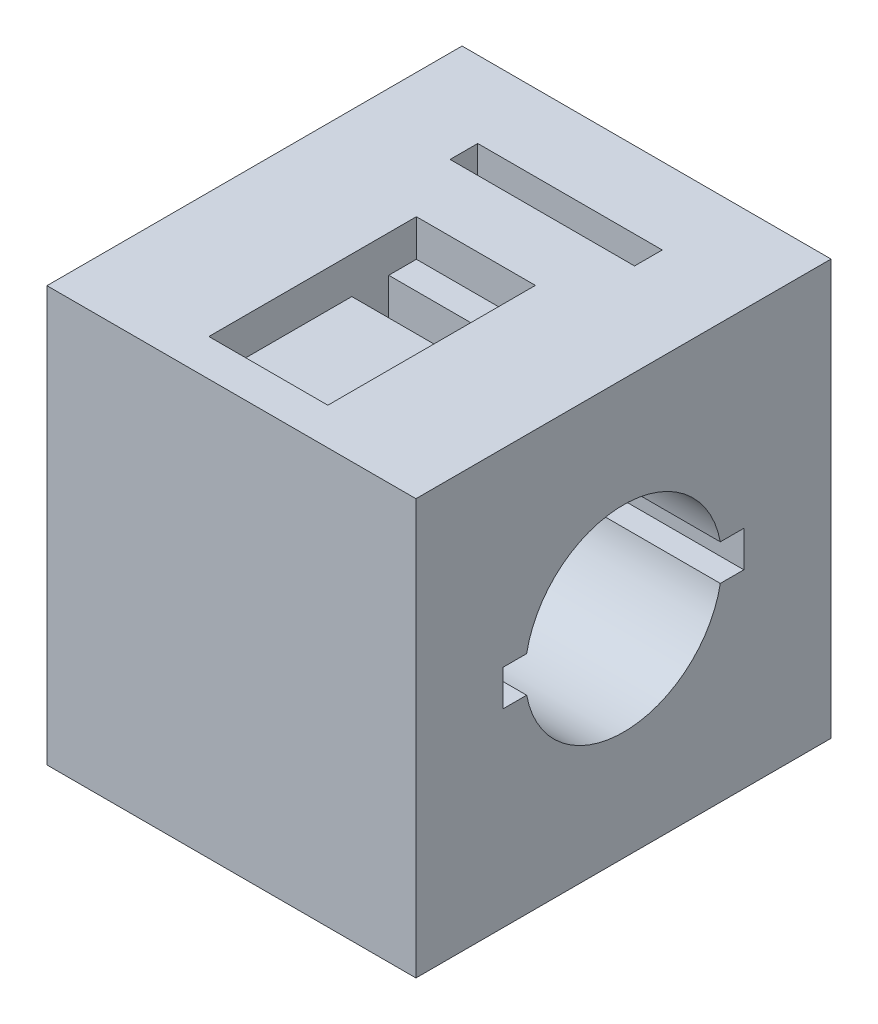
SolidWorks part; units mm, degrees
ref_plane "Front Plane" through (0, 0, 0) normal (0, 0, 1) x (1, 0, 0)
ref_plane "Top Plane" through (0, 0, 0) normal (0, 1, 0) x (1, 0, 0)
ref_plane "Right Plane" through (0, 0, 0) normal (1, 0, 0) x (0, 0, -1)
sketch "Sketch1" plane through (0, 0, 0) normal (1, 0, 0) x (0, 0, -1)
  line L1 (-22.5, 22.5) -> (22.5, 22.5)
  line L2 (-22.5, 22.5) -> (-22.5, -22.5)
  line L3 (-22.5, -22.5) -> (22.5, -22.5)
  line L4 (22.5, 22.5) -> (22.5, -22.5)
  line L5 (-22.5, 22.5) -> (22.5, -22.5) construction
  line L6 (-22.5, -22.5) -> (22.5, 22.5) construction
  point P0 (0, 0)
  dimension "D1" = 45
  dimension "D2" = 45
extrude "Boss-Extrude1" add sketch "Sketch1" along normal blind 40
sketch "Sketch2" plane through (40, 0, 0) normal (1, 0, 0) x (0, 0, -1)
  circle A0 centre (0, 0) radius 10.675
  dimension "D1" = 21.35
extrude "Cut-Extrude1" cut sketch "Sketch2" against normal through all
sketch "Sketch3" plane through (40, 0, 0) normal (1, 0, 0) x (0, 0, -1)
  line L0 (10.4954, 1.95) -> (13.0454, 1.95)
  line L1 (13.0454, 1.95) -> (13.0454, -1.95)
  line L2 (13.0454, -1.95) -> (10.4954, -1.95)
  circle A0 centre (0, 0) radius 10.675 construction
  arc A1 (10.4954, 1.95) -> (10.4954, -1.95) centre (10.4954, 0) ccw
  point P6 (13.0454, 0)
  dimension "D1" = 2.55
  dimension "D2" = 3.9
extrude "Cut-Extrude2" cut sketch "Sketch3" against normal through all
mirror "Mirror1" about plane through (0, 0, 0) normal (0, 0, 1) of "Cut-Extrude2"
sketch "Sketch4" plane through (0, 22.5, 0) normal (0, 1, 0) x (1, 0, 0)
  line L0 (20, 22.5) -> (20, -22.5) construction
  line L1 (40, 22.5) -> (0, 22.5) construction
  line L2 (40, -22.5) -> (0, -22.5) construction
  line L4 (13.55, 4) -> (26.45, 4)
  line L5 (13.55, 4) -> (13.55, -18.5)
  line L6 (13.55, -18.5) -> (26.45, -18.5)
  line L7 (26.45, 4) -> (26.45, -18.5)
  line L8 (13.55, 4) -> (26.45, -18.5) construction
  line L9 (13.55, -18.5) -> (26.45, 4) construction
  point P6 (20, 0)
  point P11 (20, 0)
  point P12 (20, -7.25)
  dimension "D1" = 12.9
  dimension "D2" = 22.5
  dimension "D3" = 4
extrude "Cut-Extrude3" cut sketch "Sketch4" against normal blind 4
sketch "Sketch5" plane through (0, 18.5, 0) normal (0, 1, 0) x (1, 0, 0)
  line L0 (13.55, 4) -> (13.55, -18.5) construction
  line L1 (13.55, 1) -> (26.45, 1)
  line L2 (13.55, 1) -> (13.55, -3)
  line L3 (13.55, -3) -> (26.45, -3)
  line L4 (26.45, 1) -> (26.45, -3)
  line L5 (26.45, -18.5) -> (26.45, 4) construction
  line L6 (26.45, 4) -> (13.55, 4) construction
  dimension "D1" = 4
  dimension "D2" = 3
extrude "Cut-Extrude4" cut sketch "Sketch5" against normal blind 6
sketch "Sketch6" plane through (0, 22.5, 0) normal (0, 1, 0) x (1, 0, 0)
  line L0 (26.45, 4) -> (13.55, 4) construction
  line L1 (10, 11.2) -> (30, 11.2)
  line L2 (10, 11.2) -> (10, 14.2)
  line L3 (10, 14.2) -> (30, 14.2)
  line L4 (30, 11.2) -> (30, 14.2)
  point P6 (20, 11.2)
  point P7 (20, 4)
  dimension "D1" = 7.2
  dimension "D2" = 3
  dimension "D3" = 20
extrude "Cut-Extrude5" cut sketch "Sketch6" against normal blind 6
equation "\"Stock Diameter\"= 21.35"
equation "\"Knotch Width\" = 3.9"
equation "\"Knotch Height\"= 2.55"
equation "\"D1@Sketch2\"=\"Stock Diameter\""
equation "\"D1@Sketch3\"=\"Knotch Height\""
equation "\"D2@Sketch3\"=\"Knotch Width\""
